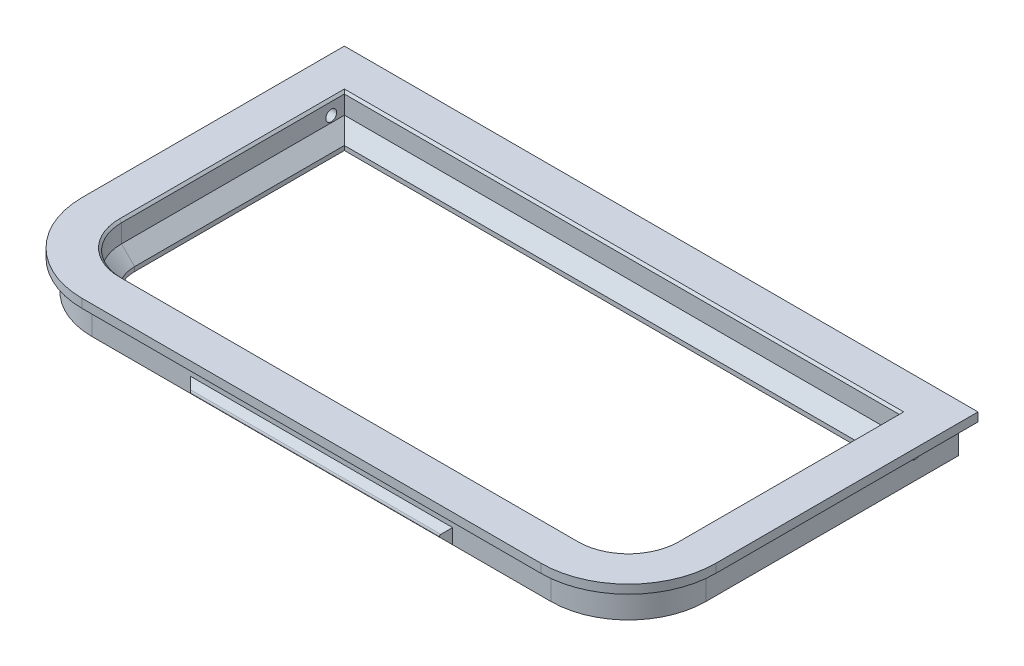
SolidWorks part; units mm, degrees
material "ПК/АБС"
ref_plane "Спереди" through (0, 0, 0) normal (0, 0, 1) x (1, 0, 0)
ref_plane "Сверху" through (0, 0, 0) normal (0, 1, 0) x (1, 0, 0)
ref_plane "Справа" through (0, 0, 0) normal (1, 0, 0) x (0, 0, -1)
sketch "Эскиз1" plane through (0, 0, 0) normal (0, 1, 0) x (1, 0, 0)
  line L1 (-72.5, -40) -> (72.5, -40)
  line L2 (-72.5, -40) -> (-72.5, 40)
  line L3 (-72.5, 40) -> (72.5, 40)
  line L4 (72.5, -40) -> (72.5, 40)
  line L5 (-72.5, -40) -> (72.5, 40) construction
  line L6 (-72.5, 40) -> (72.5, -40) construction
  point P0 (0, 0)
  dimension "D1" = 145
  dimension "D2" = 80
extrude "Бобышка-Вытянуть1" add sketch "Эскиз1" along normal blind 2
fillet "Скругление1" radius 20 2 edges at (-72.5, 1, 40) (72.5, 1, 40)
sketch "Эскиз2" plane through (0, 2, 0) normal (0, 1, 0) x (1, 0, 0)
  line L8 (-63.5, 31) -> (-63.5, -20)
  line L9 (-52.5, -31) -> (52.5, -31)
  line L10 (63.5, -20) -> (63.5, 31)
  line L11 (63.5, 31) -> (-63.5, 31)
  line L12 (-63.5, 31) -> (-63.5, -20)
  line L13 (-52.5, -31) -> (52.5, -31)
  line L14 (63.5, -20) -> (63.5, 31)
  line L15 (63.5, 31) -> (-63.5, 31)
  arc A4 (-63.5, -20) -> (-52.5, -31) centre (-52.5, -20) ccw
  arc A5 (52.5, -31) -> (63.5, -20) centre (52.5, -20) ccw
  arc A6 (-63.5, -20) -> (-52.5, -31) centre (-52.5, -20) ccw
  arc A7 (52.5, -31) -> (63.5, -20) centre (52.5, -20) ccw
  dimension "D1" = 9
extrude "Вырез-Вытянуть1" cut sketch "Эскиз2" against normal blind 2
sketch "Эскиз3" plane through (0, 0, 0) normal (0, -1, 0) x (1, 0, 0)
  line L15 (-63.5, -31) -> (-63.5, 20) construction
  line L16 (63.5, -31) -> (-63.5, -31) construction
  line L17 (63.5, 20) -> (63.5, -31) construction
  line L18 (-52.5, 31) -> (52.5, 31) construction
  line L19 (70.25, -37.75) -> (70.25, 20)
  line L20 (-70.25, -37.75) -> (70.25, -37.75)
  line L21 (-70.25, 20) -> (-70.25, -37.75)
  line L22 (52.5, 37.75) -> (-52.5, 37.75)
  line L23 (70.25, -37.75) -> (70.25, 20)
  line L24 (-70.25, -37.75) -> (70.25, -37.75)
  line L25 (-70.25, 20) -> (-70.25, -37.75)
  line L26 (52.5, 37.75) -> (-52.5, 37.75)
  line L27 (-63.5, -31) -> (-63.5, 20)
  line L28 (63.5, -31) -> (-63.5, -31)
  line L29 (63.5, 20) -> (63.5, -31)
  line L30 (-52.5, 31) -> (52.5, 31)
  arc A6 (-52.5, 31) -> (-63.5, 20) centre (-52.5, 20) ccw construction
  arc A7 (63.5, 20) -> (52.5, 31) centre (52.5, 20) ccw construction
  arc A8 (70.25, 20) -> (52.5, 37.75) centre (52.5, 20) ccw
  arc A9 (-52.5, 37.75) -> (-70.25, 20) centre (-52.5, 20) ccw
  arc A10 (70.25, 20) -> (52.5, 37.75) centre (52.5, 20) ccw
  arc A11 (-52.5, 37.75) -> (-70.25, 20) centre (-52.5, 20) ccw
  arc A12 (-52.5, 31) -> (-63.5, 20) centre (-52.5, 20) ccw
  arc A13 (63.5, 20) -> (52.5, 31) centre (52.5, 20) ccw
  dimension "D1" = 6.75
extrude "Бобышка-Вытянуть2" add sketch "Эскиз3" along normal blind 2
sketch "Эскиз5" plane through (0, 0, 0) normal (1, 0, 0) x (0, 0, -1)
  line L0 (-20, 0) -> (40, 0) construction
  line L7 (37.75, -2) -> (31, -2)
  line L9 (31, -2) -> (31, -6.7)
  line L10 (31, -6.7) -> (37.75, -6.7)
  line L11 (37.75, -6.7) -> (39.45, -5)
  line L12 (39.45, -5) -> (37.75, -3.3)
  line L13 (37.75, -3.3) -> (37.75, -2)
  line L14 (31, -2) -> (31, 2) construction
  line L15 (31, -2) -> (31, 2) construction
  dimension "D1" = 5
  dimension "D2" = 1.7
extrude "Бобышка-Вытянуть4" add sketch "Эскиз5" along normal mid plane 120
sketch "Эскиз13" plane through (0, 0, 0) normal (1, 0, 0) x (0, 0, -1)
  line L0 (31, -6.7) -> (37.75, -6.7) construction
  line L1 (-31, -2) -> (-31, -6.7)
  line L2 (-31, -6.7) -> (-37.75, -6.7)
  line L3 (-37.75, -6.7) -> (-39.45, -5)
  line L4 (-39.45, -5) -> (-37.75, -3.3)
  line L5 (-37.75, -3.3) -> (-37.75, -2)
  line L6 (-37.75, -2) -> (-31, -2)
  line L7 (-31, -2) -> (-31, 2) construction
  line L8 (-31, -2) -> (-31, 2) construction
  point P3 (0, 0)
  point P7 (0, 0)
  point P8 (-37.2468, -10.3907)
  point P10 (-37.75, -2)
  dimension "D1" = 1.7
extrude "Бобышка-Вытянуть10" add sketch "Эскиз13" along normal mid plane 10
sketch "Эскиз6" plane through (0, 0, 0) normal (1, 0, 0) x (0, 0, -1)
  line L12 (-39.45, -5) -> (-37.75, -6.7)
  line L13 (-37.75, -6.7) -> (-31, -6.7)
  line L14 (-31, -6.7) -> (-31, -2)
  line L15 (-31, -2) -> (-36.0877, -2)
  line L16 (-37.75, -2) -> (-37.75, -3.3)
  line L17 (-37.75, -3.3) -> (-39.45, -5)
  line L20 (-36.0877, -2) -> (-37.75, -2)
extrude "Бобышка-Вытянуть5" add sketch "Эскиз6" along normal mid plane 60
fillet "Скругление2" radius 0.5 2 edges at (0, -5, -39.45) (0, -5, 39.45)
sketch "Эскиз7" plane through (0, -2, 0) normal (0, -1, 0) x (1, 0, 0)
  line L7 (-30, 31) -> (-30, 37.75)
  line L8 (-52.5, 31) -> (-30, 31)
  line L10 (30, 37.75) -> (30, 31)
  line L11 (-70.25, 20) -> (-70.25, -37.75)
  line L12 (-70.25, -37.75) -> (-60, -37.75)
  line L13 (-60, -37.75) -> (-60, -31)
  line L14 (-60, -31) -> (-63.5, -31)
  line L15 (-63.5, -31) -> (-63.5, 20)
  line L16 (-52.5, 31) -> (-30, 31)
  line L19 (-70.25, 20) -> (-70.25, -37.75)
  line L20 (-70.25, -37.75) -> (-60, -37.75)
  line L21 (-60, -37.75) -> (-60, -31)
  line L22 (-60, -31) -> (-63.5, -31)
  line L23 (-63.5, -31) -> (-63.5, 20)
  line L25 (30, 31) -> (52.5, 31)
  line L26 (63.5, 20) -> (63.5, -31)
  line L27 (63.5, -31) -> (60, -31)
  line L28 (60, -31) -> (60, -37.75)
  line L29 (60, -37.75) -> (70.25, -37.75)
  line L30 (70.25, -37.75) -> (70.25, 20)
  line L33 (30, 31) -> (52.5, 31)
  line L34 (63.5, 20) -> (63.5, -31)
  line L35 (63.5, -31) -> (60, -31)
  line L36 (60, -31) -> (60, -37.75)
  line L37 (60, -37.75) -> (70.25, -37.75)
  line L38 (70.25, -37.75) -> (70.25, 20)
  line L41 (-30, 37.75) -> (-52.5, 37.75)
  line L42 (-30, 37.75) -> (-52.5, 37.75)
  line L44 (52.5, 37.75) -> (30, 37.75)
  line L45 (52.5, 37.75) -> (30, 37.75)
  line L48 (-30, 31) -> (-30, 37.75)
  line L49 (30, 37.75) -> (30, 31)
  arc A2 (-52.5, 37.75) -> (-70.25, 20) centre (-52.5, 20) ccw
  arc A3 (-52.5, 31) -> (-63.5, 20) centre (-52.5, 20) ccw
  arc A4 (-52.5, 37.75) -> (-70.25, 20) centre (-52.5, 20) ccw
  arc A5 (-52.5, 31) -> (-63.5, 20) centre (-52.5, 20) ccw
  arc A6 (63.5, 20) -> (52.5, 31) centre (52.5, 20) ccw
  arc A7 (70.25, 20) -> (52.5, 37.75) centre (52.5, 20) ccw
  arc A8 (63.5, 20) -> (52.5, 31) centre (52.5, 20) ccw
  arc A9 (70.25, 20) -> (52.5, 37.75) centre (52.5, 20) ccw
  dimension "D1" = 0
  dimension "D2" = 0
extrude "Бобышка-Вытянуть6" add sketch "Эскиз7" along normal up to surface (4.7 mm away) up to face at (0, -6.7, 34.375)
sketch "Эскиз10" plane through (0, -6.7, 0) normal (0, -1, 0) x (1, 0, 0)
  line L9 (52.5, 31) -> (-52.5, 31) construction
  line L10 (52.5, 31) -> (-52.5, 31)
  line L11 (52.5, 28) -> (-52.5, 28)
  line L12 (-60.5, 20) -> (-60.5, -28)
  line L13 (60.5, -28) -> (-60.5, -28)
  line L14 (-63.5, 20) -> (-63.5, -31) construction
  line L15 (63.5, -31) -> (-63.5, -31) construction
  line L16 (63.5, -31) -> (63.5, 20) construction
  line L18 (60.5, -28) -> (60.5, 20)
  line L26 (-63.5, 20) -> (-63.5, -31)
  line L27 (63.5, -31) -> (-63.5, -31)
  line L28 (63.5, -31) -> (63.5, 20)
  arc A4 (-52.5, 28) -> (-60.5, 20) centre (-52.5, 20) ccw
  arc A5 (60.5, 20) -> (52.5, 28) centre (52.5, 20) ccw
  arc A7 (-52.5, 31) -> (-63.5, 20) centre (-52.5, 20) ccw construction
  arc A8 (63.5, 20) -> (52.5, 31) centre (52.5, 20) ccw construction
  arc A13 (-52.5, 31) -> (-63.5, 20) centre (-52.5, 20) ccw
  arc A14 (63.5, 20) -> (52.5, 31) centre (52.5, 20) ccw
  dimension "D1" = 3
extrude "Бобышка-Вытянуть9" add sketch "Эскиз10" against normal blind 1
chamfer "Фаска2" distance 3 angle 45 6 edges at (0, -5.7, -31) (63.5, -5.7, -5.5) (-63.5, -5.7, -5.5) (60.2782, -5.7, 27.7782) (-60.2782, -5.7, 27.7782) (0, -5.7, 31)
sketch "Эскиз11" plane through (70.25, 0, 0) normal (1, 0, 0) x (0, 0, -1)
  line L0 (40, 2) -> (40, 0) construction
  line L1 (-20, 2) -> (40, 2) construction
  circle A0 centre (28, -1.25) radius 1.25
  dimension "D1" = 2.5
  dimension "D2" = 12
  dimension "D3" = 3.25
extrude "Вырез-Вытянуть2" cut sketch "Эскиз11" against normal through all
chamfer "Фаска3" distance 0.5 angle 45 6 edges at (63.5, 2, -5.5) (60.2782, 2, 27.7782) (0, 2, 31) (-60.2782, 2, 27.7782) (-63.5, 2, -5.5) (0, 2, -31)
sketch "Эскиз12" plane through (0, 0, 0) normal (0, -1, 0) x (1, 0, 0)
  line L0 (-30, 37.75) -> (-28, 39.75)
  line L1 (-28, 39.75) -> (-30, 39.75)
  line L2 (-30, 39.75) -> (-30, 37.75)
  line L3 (30, 37.75) -> (30, 39.75)
  line L4 (30, 39.75) -> (28, 39.75)
  line L5 (28, 39.75) -> (30, 37.75)
  line L6 (-60, -37.75) -> (-60, -39.75)
  line L7 (-60, -39.75) -> (-58, -39.75)
  line L8 (-58, -39.75) -> (-60, -37.75)
  line L9 (60, -37.75) -> (58, -39.75)
  line L10 (58, -39.75) -> (60, -39.75)
  line L11 (60, -39.75) -> (60, -37.75)
  dimension "D1" = 2
extrude "Вырез-Вытянуть3" cut sketch "Эскиз12" along normal through all
